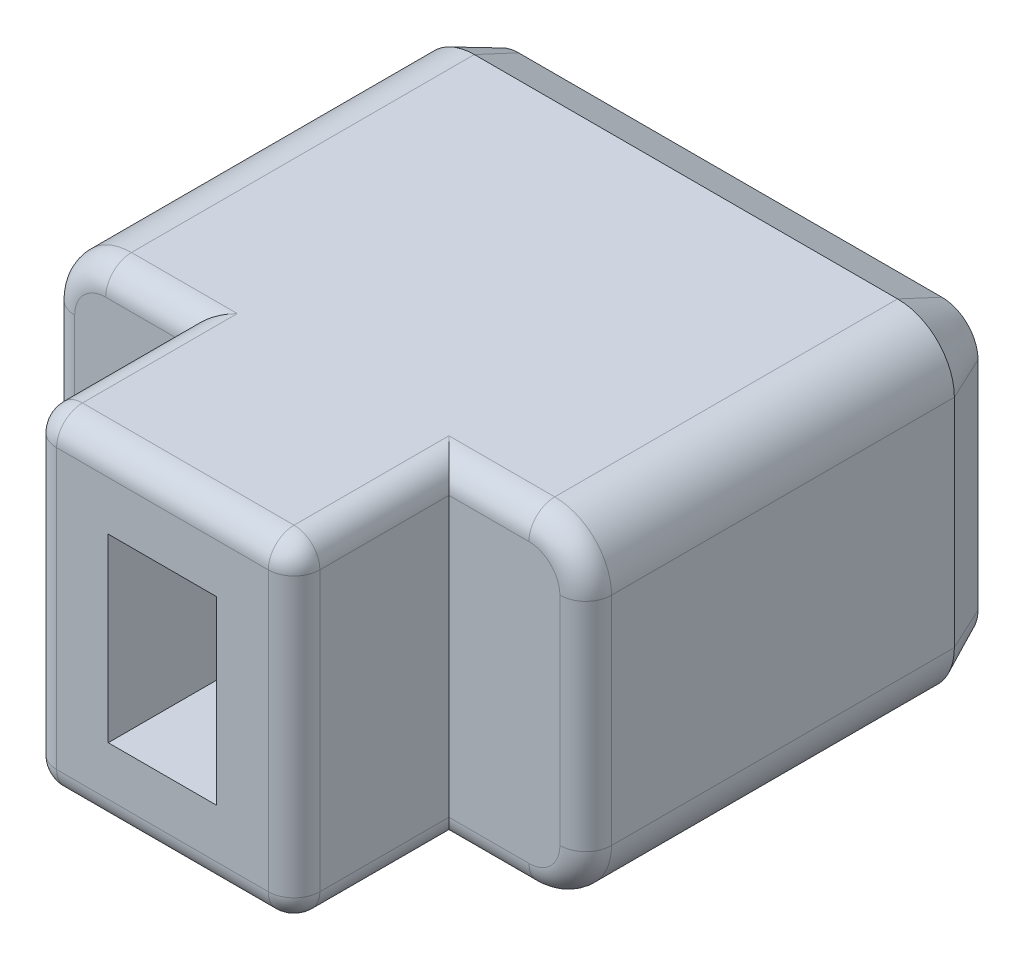
SolidWorks part; units mm, degrees
ref_plane "Plan de face" through (0, 0, 0) normal (0, 0, 1) x (1, 0, 0)
ref_plane "Plan de dessus" through (0, 0, 0) normal (0, 1, 0) x (1, 0, 0)
ref_plane "Plan de droite" through (0, 0, 0) normal (1, 0, 0) x (0, 0, -1)
sketch "Esquisse2" plane through (0, 0, 0) normal (0, 0, 1) x (1, 0, 0)
  line L1 (1.1, 0) -> (9.3, 0)
  line L2 (0, 1.1) -> (0, 5.3)
  line L3 (1.1, 6.4) -> (9.3, 6.4)
  line L4 (10.4, 1.1) -> (10.4, 5.3)
  arc A0 (9.3, 6.4) -> (10.4, 5.3) centre (9.3, 5.3) cw
  arc A1 (9.3, 0) -> (10.4, 1.1) centre (9.3, 1.1) ccw
  arc A2 (1.1, 0) -> (0, 1.1) centre (1.1, 1.1) cw
  arc A3 (0, 5.3) -> (1.1, 6.4) centre (1.1, 5.3) cw
  point P7 (10.4, 6.4)
  point P12 (0, 0)
  point P15 (0, 6.4)
  dimension "D3" = 1.1
  dimension "D1" = 10.4
  dimension "D2" = 6.4
extrude "Boss.-Extru.1" add sketch "Esquisse2" along normal blind 11
sketch "Esquisse3" plane through (0, 0, 11) normal (0, 0, 1) x (1, 0, 0)
  line L0 (0, 5.3) -> (0, 1.1) construction
  line L1 (4.15, 4.95) -> (6.25, 4.95)
  line L2 (4.15, 4.95) -> (4.15, 1.45)
  line L3 (4.15, 1.45) -> (6.25, 1.45)
  line L4 (6.25, 4.95) -> (6.25, 1.45)
  line L5 (10.4, 1.1) -> (10.4, 5.3) construction
  line L6 (9.3, 6.4) -> (1.1, 6.4) construction
  line L7 (1.1, 0) -> (9.3, 0) construction
  dimension "D1" = 2.1
  dimension "D2" = 3.5
  dimension "D3" = 4.15
  dimension "D4" = 4.15
  dimension "D5" = 1.45
  dimension "D6" = 1.45
extrude "Enlèv. mat.-Extru.1" cut sketch "Esquisse3" against normal blind 3
sketch "Esquisse4" plane through (0, 0, 11) normal (0, 0, 1) x (1, 0, 0)
  line L0 (2.65, 6.4) -> (2.65, 0)
  line L1 (9.3, 6.4) -> (1.1, 6.4) construction
  line L2 (1.1, 0) -> (9.3, 0) construction
  line L3 (2.65, 0) -> (7.75, 0)
  line L4 (7.75, 0) -> (7.75, 6.4)
  line L5 (7.75, 6.4) -> (2.65, 6.4)
  line L6 (4.15, 4.95) -> (4.15, 1.45) construction
  line L7 (6.25, 1.45) -> (6.25, 4.95) construction
  dimension "D1" = 1.5
  dimension "D2" = 1.5
extrude "Enlèv. mat.-Extru.2" cut sketch "Esquisse4" against normal blind 3 flip side to cut
fillet "Congé1" radius 0.5 18 edges at (8.525, 0, 8) (10.0778, 0.3222, 8) (10.4, 3.2, 8) (10.0778, 6.0778, 8) (1.875, 6.4, 8) (0.3222, 6.0778, 8) (1.875, 0, 8) (0.3222, 0.3222, 8) (7.75, 6.4, 9.5) (2.65, 6.4, 9.5) (7.75, 0, 9.5) (2.65, 0, 9.5) (2.65, 3.2, 11) (5.2, 6.4, 11) (7.75, 3.2, 11) (5.2, 0, 11) (8.525, 6.4, 8) (0, 3.2, 8)
chamfer "Chanfrein1" distance 0.4 angle 65 8 edges at (5.2, 0, 0) (10.0778, 0.3222, 0) (0.3222, 0.3222, 0) (10.4, 3.2, 0) (0, 3.2, 0) (10.0778, 6.0778, 0) (0.3222, 6.0778, 0) (5.2, 6.4, 0) first distance on face at (5.2, 3.2, 0)
sketch "Esquisse5" plane through (0, 0, 0) normal (0, 0, -1) x (-1, 0, 0)
  line L0 (-0.4, 5.3) -> (-10, 5.3) construction
  arc A0 (-9.3, 6) -> (-10, 5.3) centre (-9.3, 5.3) ccw construction
  text T0 "6" font "Century Gothic" height 4
extrude "Enlèv. mat.-Extru.3" cut sketch "Esquisse5" against normal blind 0.3
extrude "Boss.-Extru.2" add sketch "Esquisse5<2>" along normal blind 0.3 separate body
sketch "Esquisse5<2>" plane through (0, 0, 0) normal (0, 0, -1) x (-1, 0, 0) same geometry as "Esquisse5"
